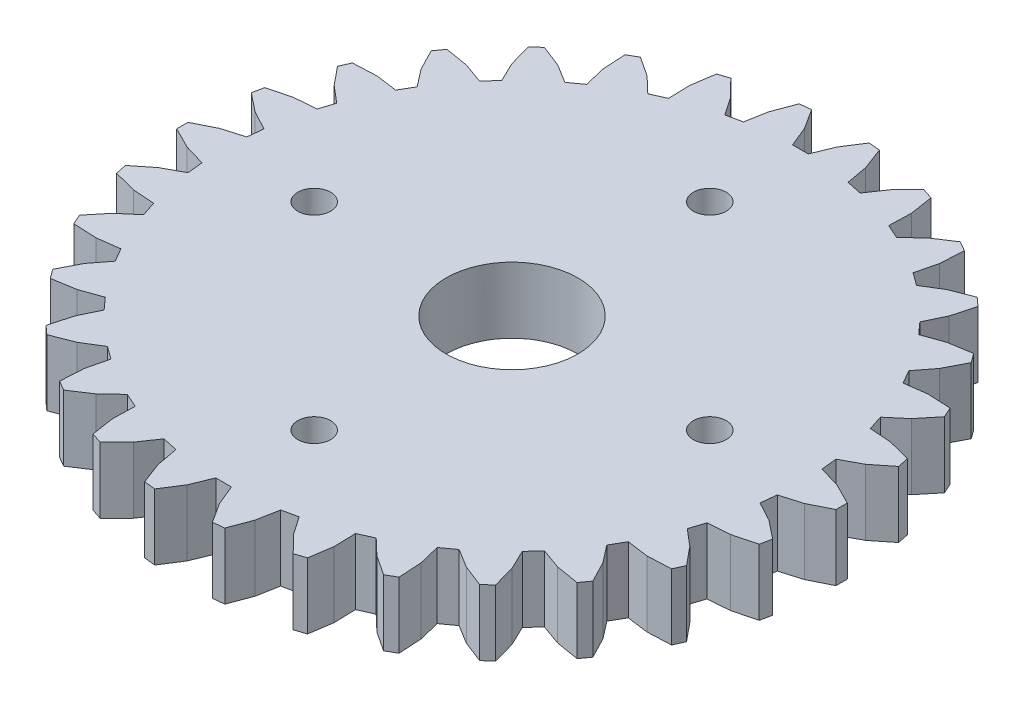
SolidWorks part; units mm, degrees
material "Acrylic (Medium-high impact)"
ref_plane "Front Plane" through (0, 0, 0) normal (0, 0, 1) x (1, 0, 0)
ref_plane "Top Plane" through (0, 0, 0) normal (0, 1, 0) x (1, 0, 0)
ref_plane "Right Plane" through (0, 0, 0) normal (1, 0, 0) x (0, 0, -1)
sketch "Sketch1" plane through (0, 0, 0) normal (0, 1, 0) x (1, 0, 0)
  line L0 (67.8387, 65.5179) -> (69.435, 65.0497)
  line L1 (69.435, 65.0497) -> (71.0262, 64.252)
  line L2 (71.0262, 64.252) -> (71.0262, 63.394)
  line L3 (71.0262, 63.394) -> (69.435, 62.5962)
  line L4 (69.435, 62.5962) -> (67.8387, 62.1281)
  line L5 (67.8387, 62.1281) -> (67.7144, 60.9457)
  line L6 (67.7144, 60.9457) -> (69.1786, 60.156)
  line L7 (69.1786, 60.156) -> (70.5691, 59.0447)
  line L8 (70.5691, 59.0447) -> (70.3908, 58.2056)
  line L9 (70.3908, 58.2056) -> (68.6684, 57.756)
  line L10 (68.6684, 57.756) -> (67.0096, 57.6301)
  line L11 (67.0096, 57.6301) -> (66.6423, 56.4993)
  line L12 (66.6423, 56.4993) -> (67.9102, 55.4225)
  line L13 (67.9102, 55.4225) -> (69.0393, 54.0464)
  line L14 (69.0393, 54.0464) -> (68.6904, 53.2627)
  line L15 (68.6904, 53.2627) -> (66.9123, 53.181)
  line L16 (66.9123, 53.181) -> (65.2636, 53.4028)
  line L17 (65.2636, 53.4028) -> (64.669, 52.3732)
  line L18 (64.669, 52.3732) -> (65.6854, 51.0562)
  line L19 (65.6854, 51.0562) -> (66.5038, 49.4753)
  line L20 (66.5038, 49.4753) -> (65.9995, 48.7814)
  line L21 (65.9995, 48.7814) -> (64.2432, 49.0712)
  line L22 (64.2432, 49.0712) -> (62.6766, 49.6308)
  line L23 (62.6766, 49.6308) -> (61.8811, 48.7473)
  line L24 (61.8811, 48.7473) -> (62.6014, 47.2478)
  line L25 (62.6014, 47.2478) -> (63.0732, 45.5314)
  line L26 (63.0732, 45.5314) -> (62.4357, 44.9574)
  line L27 (62.4357, 44.9574) -> (60.778, 45.606)
  line L28 (60.778, 45.606) -> (59.3621, 46.4791)
  line L29 (59.3621, 46.4791) -> (58.4003, 45.7802)
  line L30 (58.4003, 45.7802) -> (58.793, 44.1638)
  line L31 (58.793, 44.1638) -> (58.8977, 42.3868)
  line L32 (58.8977, 42.3868) -> (58.1548, 41.9579)
  line L33 (58.1548, 41.9579) -> (56.6682, 42.9369)
  line L34 (56.6682, 42.9369) -> (55.4646, 44.0854)
  line L35 (55.4646, 44.0854) -> (54.3785, 43.6018)
  line L36 (54.3785, 43.6018) -> (54.4267, 41.939)
  line L37 (54.4267, 41.939) -> (54.1596, 40.1792)
  line L38 (54.1596, 40.1792) -> (53.3436, 39.914)
  line L39 (53.3436, 39.914) -> (52.0932, 41.1808)
  line L40 (52.0932, 41.1808) -> (51.1547, 42.5544)
  line L41 (51.1547, 42.5544) -> (49.9918, 42.3072)
  line L42 (49.9918, 42.3072) -> (49.6932, 40.6706)
  line L43 (49.6932, 40.6706) -> (49.066, 39.0048)
  line L44 (49.066, 39.0048) -> (48.2128, 38.9151)
  line L45 (48.2128, 38.9151) -> (47.253, 40.4142)
  line L46 (47.253, 40.4142) -> (46.6207, 41.9528)
  line L47 (46.6207, 41.9528) -> (45.4317, 41.9528)
  line L48 (45.4317, 41.9528) -> (44.7994, 40.4142)
  line L49 (44.7994, 40.4142) -> (43.8396, 38.9151)
  line L50 (43.8396, 38.9151) -> (42.9864, 39.0048)
  line L51 (42.9864, 39.0048) -> (42.3592, 40.6706)
  line L52 (42.3592, 40.6706) -> (42.0606, 42.3072)
  line L53 (42.0606, 42.3072) -> (40.8977, 42.5544)
  line L54 (40.8977, 42.5544) -> (39.9592, 41.1808)
  line L55 (39.9592, 41.1808) -> (38.7088, 39.914)
  line L56 (38.7088, 39.914) -> (37.8928, 40.1792)
  line L57 (37.8928, 40.1792) -> (37.6257, 41.939)
  line L58 (37.6257, 41.939) -> (37.6739, 43.6018)
  line L59 (37.6739, 43.6018) -> (36.5878, 44.0854)
  line L60 (36.5878, 44.0854) -> (35.3842, 42.9369)
  line L61 (35.3842, 42.9369) -> (33.8976, 41.9579)
  line L62 (33.8976, 41.9579) -> (33.1547, 42.3868)
  line L63 (33.1547, 42.3868) -> (33.2594, 44.1638)
  line L64 (33.2594, 44.1638) -> (33.6521, 45.7802)
  line L65 (33.6521, 45.7802) -> (32.6903, 46.4791)
  line L66 (32.6903, 46.4791) -> (31.2744, 45.606)
  line L67 (31.2744, 45.606) -> (29.6167, 44.9574)
  line L68 (29.6167, 44.9574) -> (28.9792, 45.5314)
  line L69 (28.9792, 45.5314) -> (29.451, 47.2478)
  line L70 (29.451, 47.2478) -> (30.1713, 48.7473)
  line L71 (30.1713, 48.7473) -> (29.3758, 49.6308)
  line L72 (29.3758, 49.6308) -> (27.8092, 49.0712)
  line L73 (27.8092, 49.0712) -> (26.0529, 48.7814)
  line L74 (26.0529, 48.7814) -> (25.5486, 49.4753)
  line L75 (25.5486, 49.4753) -> (26.367, 51.0562)
  line L76 (26.367, 51.0562) -> (27.3834, 52.3732)
  line L77 (27.3834, 52.3732) -> (26.7888, 53.4028)
  line L78 (26.7888, 53.4028) -> (25.1401, 53.181)
  line L79 (25.1401, 53.181) -> (23.362, 53.2627)
  line L80 (23.362, 53.2627) -> (23.0131, 54.0464)
  line L81 (23.0131, 54.0464) -> (24.1422, 55.4225)
  line L82 (24.1422, 55.4225) -> (25.4101, 56.4993)
  line L83 (25.4101, 56.4993) -> (25.0428, 57.6301)
  line L84 (25.0428, 57.6301) -> (23.384, 57.756)
  line L85 (23.384, 57.756) -> (21.6616, 58.2056)
  line L86 (21.6616, 58.2056) -> (21.4833, 59.0447)
  line L87 (21.4833, 59.0447) -> (22.8738, 60.156)
  line L88 (22.8738, 60.156) -> (24.338, 60.9457)
  line L89 (24.338, 60.9457) -> (24.2137, 62.1281)
  line L90 (24.2137, 62.1281) -> (22.6174, 62.5962)
  line L91 (22.6174, 62.5962) -> (21.0262, 63.394)
  line L92 (21.0262, 63.394) -> (21.0262, 64.252)
  line L93 (21.0262, 64.252) -> (22.6174, 65.0497)
  line L94 (22.6174, 65.0497) -> (24.2137, 65.5179)
  line L95 (24.2137, 65.5179) -> (24.338, 66.7003)
  line L96 (24.338, 66.7003) -> (22.8738, 67.49)
  line L97 (22.8738, 67.49) -> (21.4833, 68.6013)
  line L98 (21.4833, 68.6013) -> (21.6616, 69.4404)
  line L99 (21.6616, 69.4404) -> (23.384, 69.89)
  line L100 (23.384, 69.89) -> (25.0428, 70.0159)
  line L101 (25.0428, 70.0159) -> (25.4101, 71.1467)
  line L102 (25.4101, 71.1467) -> (24.1422, 72.2235)
  line L103 (24.1422, 72.2235) -> (23.0131, 73.5996)
  line L104 (23.0131, 73.5996) -> (23.362, 74.3832)
  line L105 (23.362, 74.3832) -> (25.1401, 74.465)
  line L106 (25.1401, 74.465) -> (26.7888, 74.2432)
  line L107 (26.7888, 74.2432) -> (27.3834, 75.2728)
  line L108 (27.3834, 75.2728) -> (26.367, 76.5898)
  line L109 (26.367, 76.5898) -> (25.5486, 78.1707)
  line L110 (25.5486, 78.1707) -> (26.0529, 78.8646)
  line L111 (26.0529, 78.8646) -> (27.8092, 78.5748)
  line L112 (27.8092, 78.5748) -> (29.3758, 78.0151)
  line L113 (29.3758, 78.0151) -> (30.1713, 78.8987)
  line L114 (30.1713, 78.8987) -> (29.451, 80.3982)
  line L115 (29.451, 80.3982) -> (28.9792, 82.1145)
  line L116 (28.9792, 82.1145) -> (29.6167, 82.6886)
  line L117 (29.6167, 82.6886) -> (31.2744, 82.04)
  line L118 (31.2744, 82.04) -> (32.6903, 81.1669)
  line L119 (32.6903, 81.1669) -> (33.6521, 81.8658)
  line L120 (33.6521, 81.8658) -> (33.2594, 83.4822)
  line L121 (33.2594, 83.4822) -> (33.1547, 85.2592)
  line L122 (33.1547, 85.2592) -> (33.8976, 85.6881)
  line L123 (33.8976, 85.6881) -> (35.3842, 84.7091)
  line L124 (35.3842, 84.7091) -> (36.5878, 83.5606)
  line L125 (36.5878, 83.5606) -> (37.6739, 84.0442)
  line L126 (37.6739, 84.0442) -> (37.6257, 85.707)
  line L127 (37.6257, 85.707) -> (37.8928, 87.4668)
  line L128 (37.8928, 87.4668) -> (38.7088, 87.732)
  line L129 (38.7088, 87.732) -> (39.9592, 86.4652)
  line L130 (39.9592, 86.4652) -> (40.8977, 85.0916)
  line L131 (40.8977, 85.0916) -> (42.0606, 85.3388)
  line L132 (42.0606, 85.3388) -> (42.3592, 86.9754)
  line L133 (42.3592, 86.9754) -> (42.9864, 88.6412)
  line L134 (42.9864, 88.6412) -> (43.8396, 88.7309)
  line L135 (43.8396, 88.7309) -> (44.7994, 87.2318)
  line L136 (44.7994, 87.2318) -> (45.4317, 85.6932)
  line L137 (45.4317, 85.6932) -> (46.6207, 85.6932)
  line L138 (46.6207, 85.6932) -> (47.253, 87.2318)
  line L139 (47.253, 87.2318) -> (48.2128, 88.7309)
  line L140 (48.2128, 88.7309) -> (49.066, 88.6412)
  line L141 (49.066, 88.6412) -> (49.6932, 86.9754)
  line L142 (49.6932, 86.9754) -> (49.9918, 85.3388)
  line L143 (49.9918, 85.3388) -> (51.1547, 85.0916)
  line L144 (51.1547, 85.0916) -> (52.0932, 86.4652)
  line L145 (52.0932, 86.4652) -> (53.3436, 87.732)
  line L146 (53.3436, 87.732) -> (54.1596, 87.4668)
  line L147 (54.1596, 87.4668) -> (54.4267, 85.707)
  line L148 (54.4267, 85.707) -> (54.3785, 84.0442)
  line L149 (54.3785, 84.0442) -> (55.4646, 83.5606)
  line L150 (55.4646, 83.5606) -> (56.6682, 84.7091)
  line L151 (56.6682, 84.7091) -> (58.1548, 85.6881)
  line L152 (58.1548, 85.6881) -> (58.8977, 85.2592)
  line L153 (58.8977, 85.2592) -> (58.793, 83.4822)
  line L154 (58.793, 83.4822) -> (58.4003, 81.8658)
  line L155 (58.4003, 81.8658) -> (59.3621, 81.1669)
  line L156 (59.3621, 81.1669) -> (60.778, 82.04)
  line L157 (60.778, 82.04) -> (62.4357, 82.6886)
  line L158 (62.4357, 82.6886) -> (63.0732, 82.1145)
  line L159 (63.0732, 82.1145) -> (62.6014, 80.3982)
  line L160 (62.6014, 80.3982) -> (61.8811, 78.8987)
  line L161 (61.8811, 78.8987) -> (62.6766, 78.0151)
  line L162 (62.6766, 78.0151) -> (64.2432, 78.5748)
  line L163 (64.2432, 78.5748) -> (65.9995, 78.8646)
  line L164 (65.9995, 78.8646) -> (66.5038, 78.1707)
  line L165 (66.5038, 78.1707) -> (65.6854, 76.5898)
  line L166 (65.6854, 76.5898) -> (64.669, 75.2728)
  line L167 (64.669, 75.2728) -> (65.2636, 74.2432)
  line L168 (65.2636, 74.2432) -> (66.9123, 74.465)
  line L169 (66.9123, 74.465) -> (68.6904, 74.3832)
  line L170 (68.6904, 74.3832) -> (69.0393, 73.5996)
  line L171 (69.0393, 73.5996) -> (67.9102, 72.2235)
  line L172 (67.9102, 72.2235) -> (66.6423, 71.1467)
  line L173 (66.6423, 71.1467) -> (67.0096, 70.0159)
  line L174 (67.0096, 70.0159) -> (68.6684, 69.89)
  line L175 (68.6684, 69.89) -> (70.3908, 69.4404)
  line L176 (70.3908, 69.4404) -> (70.5691, 68.6013)
  line L177 (70.5691, 68.6013) -> (69.1786, 67.49)
  line L178 (69.1786, 67.49) -> (67.7144, 66.7003)
  line L179 (67.7144, 66.7003) -> (67.8387, 65.5179)
  line L180 (48.6394, 38.96) -> (43.413, 88.686) construction
  line L181 (21.0262, 63.823) -> (71.0262, 63.823) construction
  point P184 (46.0262, 63.823)
sketch "Sketch2" plane through (0, 0, 0) normal (0, 1, 0) x (1, 0, 0)
  line L0 (21.0262, 63.823) -> (71.0262, 63.823) construction
  circle A0 centre (46.0262, 63.823) radius 5
  circle A1 centre (31.0262, 63.823) radius 1.25
  circle A2 centre (46.0262, 78.823) radius 1.25
  circle A3 centre (61.0262, 63.823) radius 1.25
  circle A4 centre (46.0262, 48.823) radius 1.25
  point P15 (46.0262, 63.823)
  dimension "D1" = 10
  dimension "D2" = 2.5
  dimension "D3" = 15
  dimension "D4" = 4
extrude "Boss-Extrude1" add sketch "Sketch1" along normal blind 5
extrude "Cut-Extrude1" cut sketch "Sketch2" along normal up to next
ref_axis "Axis1" through (46.0262, 5, -63.823) along (0, -1, 0)
